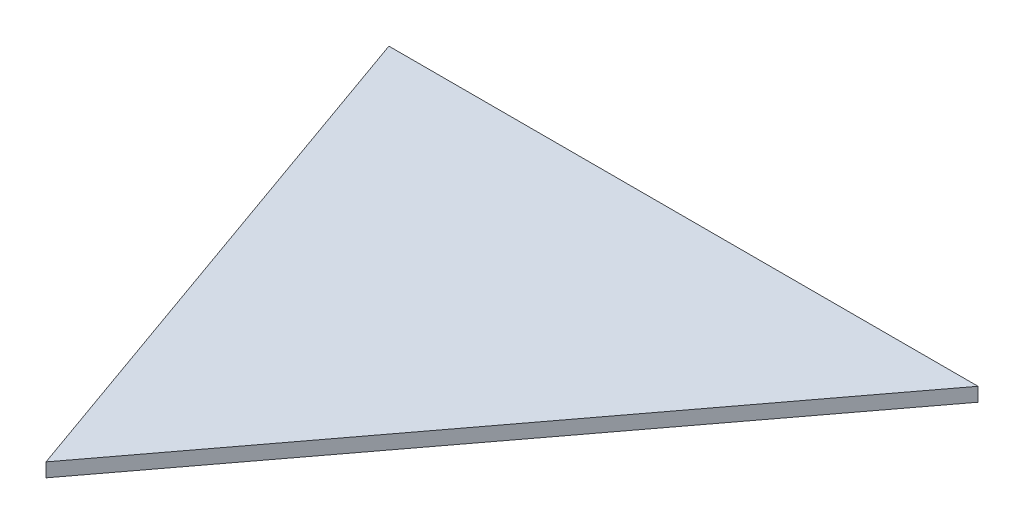
SolidWorks part; units mm, degrees
ref_plane "Front Plane" through (0, 0, 0) normal (0, 0, 1) x (1, 0, 0)
ref_plane "Top Plane" through (0, 0, 0) normal (0, 1, 0) x (1, 0, 0)
ref_plane "Right Plane" through (0, 0, 0) normal (1, 0, 0) x (0, 0, -1)
sketch "Sketch2" plane through (0, 0, 0) normal (0, 1, 0) x (1, 0, 0)
  line L0 (-57.15, 0) -> (224.536, 0)
  line L1 (224.536, 0) -> (-24.3577, -196.7539)
  line L2 (-24.3577, -196.7539) -> (-57.15, 0)
  line L3 (0, 0) -> (0, -152.4) construction
  line L4 (-31.75, -152.4) -> (31.75, -152.4) construction
  point P2 (0, 0)
  dimension "D1" = 281.686
  dimension "D2" = 57.15
  dimension "D3" = 63.5
  dimension "D4" = 152.4
extrude "Boss-Extrude1" add sketch "Sketch2" along normal blind 152.4
ref_plane "Plane1" through (-63.5, 0, 0) normal (1, 0, 0) x (0, 0, -1)
sketch "Sketch3" plane through (-63.5, 0, 0) normal (1, 0, 0) x (0, 0, -1)
  line L0 (0, 76.2) -> (-152.4, 76.2) construction
  line L1 (0, 152.4) -> (0, 0) construction
  line L2 (-152.4, 44.45) -> (-152.4, 107.95) construction
  line L3 (0, 152.4) -> (-152.4, 107.95)
  line L4 (0, 0) -> (-152.4, 44.45)
  line L5 (-152.4, 107.95) -> (-261.2571, 76.2)
  line L6 (-152.4, 44.45) -> (-261.2571, 76.2)
  line L7 (0, 152.4) -> (0, 0)
  point P7 (-152.4, 76.2)
  dimension "D1" = 152.4
  dimension "D2" = 63.5
extrude "Cut-Extrude2" cut sketch "Sketch3" along normal through all flip side to cut
shell "Shell1" thickness 6.35 removed face at (83.693, 76.2, 0)
ref_plane "Plane2" through (0, -12.7, 0) normal (0, 1, 0) x (1, 0, 0)
sketch "Sketch4" plane through (-63.5, 0, 0) normal (1, 0, 0) x (0, 0, -1)
  line L0 (0, 152.4) -> (0, 145.7854) construction
  line L1 (0, 145.7854) -> (-196.7539, 88.3989)
  line L2 (-196.7539, 95.0134) -> (-196.7539, 57.3866) construction
  line L3 (-196.7539, 88.3989) -> (-196.7539, 95.0134) construction
  line L4 (-196.7539, 95.0134) -> (0, 152.4) construction
  line L5 (-196.7539, 57.3866) -> (0, 0) construction
  line L7 (0, -70.5856) -> (-196.7539, -13.1991)
  line L8 (-196.7539, -13.1991) -> (-196.7539, 57.3866) construction
  line L9 (0, 145.7854) -> (0, -70.5856)
  line L10 (-196.7539, -13.1991) -> (-196.7539, 88.3989)
extrude "Cut-Extrude3" cut sketch "Sketch4" along normal through all
